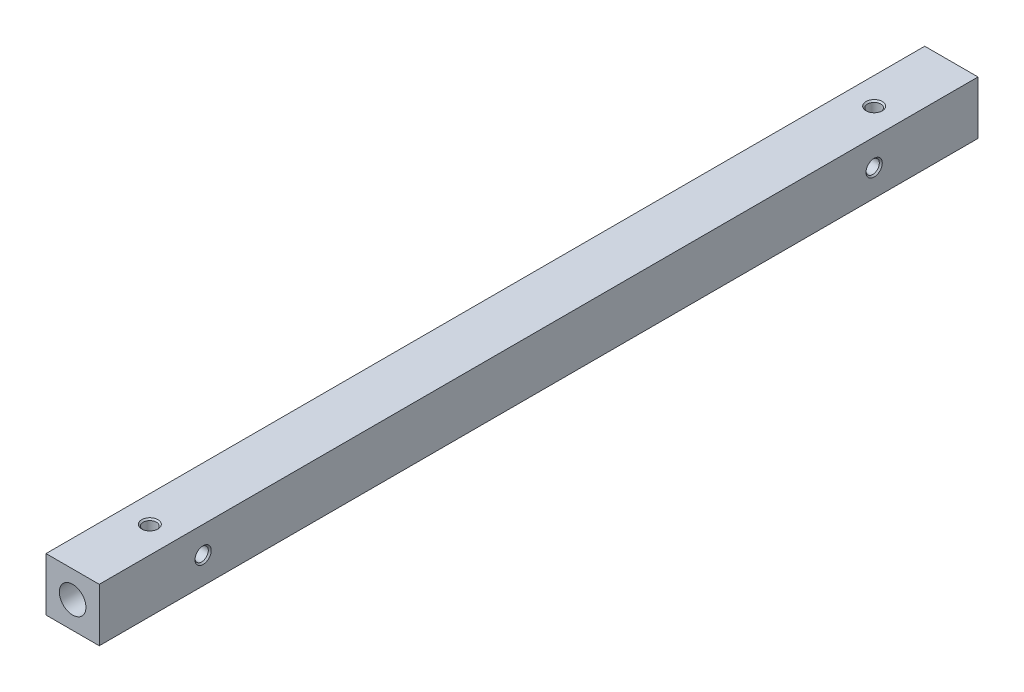
SolidWorks part; units mm, degrees
ref_plane "Plan de face" through (0, 0, 0) normal (0, 0, 1) x (1, 0, 0)
ref_plane "Plan de dessus" through (0, 0, 0) normal (0, 1, 0) x (1, 0, 0)
ref_plane "Plan de droite" through (0, 0, 0) normal (1, 0, 0) x (0, 0, -1)
sketch "Esquisse1" plane through (0, 0, 0) normal (0, 0, 1) x (1, 0, 0)
  line L0 (-5, 5) -> (5, -5) construction
  line L1 (-5, 5) -> (5, 5)
  line L2 (-5, 5) -> (-5, -5)
  line L3 (-5, -5) -> (5, -5)
  line L4 (5, 5) -> (5, -5)
  dimension "D1" = 10
extrude "Boss.-Extru.1" add sketch "Esquisse1" along normal mid plane 165
hole_wizard "Trou taraudé M3x0.51" positions "Esquisse3" profile "Esquisse2" tap size "M3x0.5" standard "Ansi Metric" end condition through all
sketch "Esquisse3" plane through (5, 0, 0) normal (1, 0, 0) x (0, 0, -1)
  point P0 (63, 0)
  point P3 (-63, 0)
sketch "Esquisse2" plane through (5, 0, -63) normal (0, 1, 0) x (0, 0, -1)
  line L0 (0, 0) -> (0, 10)
  line L1 (0, 10) -> (1.25, 10)
  line L2 (1.25, 10) -> (1.25, 0.275)
  line L3 (1.25, 0.275) -> (1.525, 0)
  line L5 (1.525, 0) -> (0, 0)
  line L6 (-1.25, 0.275) -> (-1.525, 0) construction
  line L11 (0, -6.35) -> (0, 107.95) construction
  dimension "Diamètre du trou pour taraudage jusqu'au prochain" = 2.5
  dimension "Profondeur du trou pour taraudage jusqu'au prochain" = 10
  dimension "Diamètre du fraisage entrant" = 3.05
  dimension "Angle du fraisage entrant" = 90
cosmetic thread "Filetage de perçage1" parameters "D2"=3
cosmetic thread "Filetage de perçage2" parameters "D2"=3
hole_wizard "Trou taraudé M3x0.52" positions "Esquisse5" profile "Esquisse4" tap size "M3x0.5" standard "Ansi Metric" end condition through all
sketch "Esquisse5" plane through (0, 5, 0) normal (0, 1, 0) x (1, 0, 0)
  line L0 (0, 0) -> (-36.1539, 0) construction
  line L2 (5, 82.5) -> (-5, 82.5) construction
  point P0 (0, 68)
  point P2 (0, -68)
  dimension "D1" = 68
  dimension "D2" = 14.5
sketch "Esquisse4" plane through (0, 5, -68) normal (1, 0, 0) x (0, 0, 1)
  line L0 (0, 0) -> (0, 10)
  line L1 (0, 10) -> (1.25, 10)
  line L2 (1.25, 10) -> (1.25, 0.275)
  line L3 (1.25, 0.275) -> (1.525, 0)
  line L5 (1.525, 0) -> (0, 0)
  line L6 (-1.25, 0.275) -> (-1.525, 0) construction
  line L11 (0, -6.35) -> (0, 107.95) construction
  dimension "Diamètre du trou pour taraudage jusqu'au prochain" = 2.5
  dimension "Profondeur du trou pour taraudage jusqu'au prochain" = 10
  dimension "Diamètre du fraisage entrant" = 3.05
  dimension "Angle du fraisage entrant" = 90
cosmetic thread "Filetage de perçage3" parameters "D2"=3
cosmetic thread "Filetage de perçage4" parameters "D2"=3
sketch "Esquisse6" plane through (0, 0, 82.5) normal (0, 0, 1) x (1, 0, 0)
  circle A0 centre (0, 0) radius 2.5
  dimension "D1" = 5
extrude "Enlèv. mat.-Extru.1" cut sketch "Esquisse6" against normal blind 6
